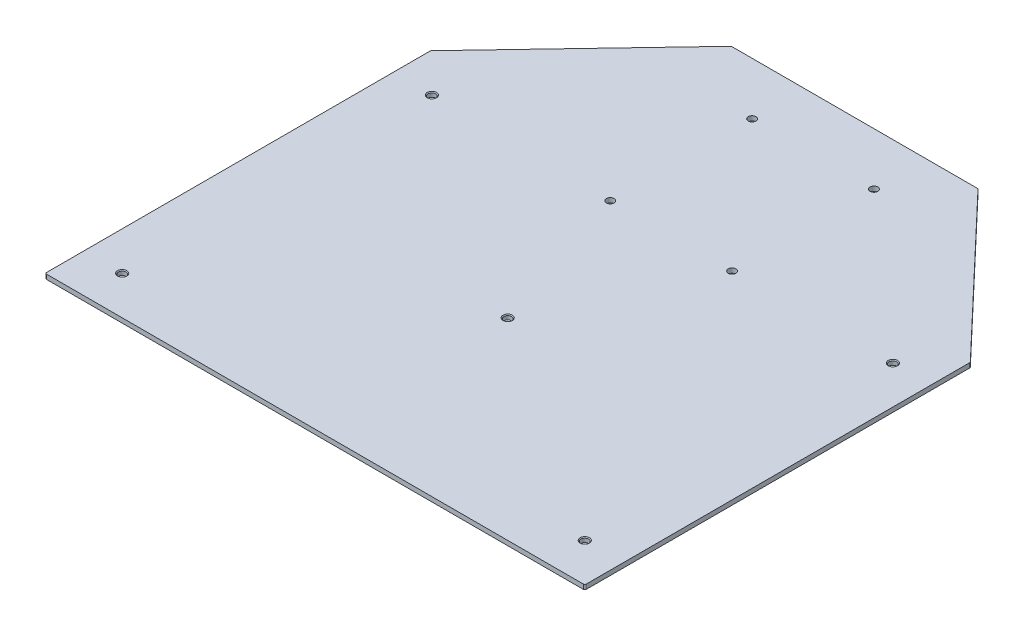
SolidWorks part; units mm, degrees
ref_plane "Front Plane" through (0, 0, 0) normal (0, 0, 1) x (1, 0, 0)
ref_plane "Top Plane" through (0, 0, 0) normal (0, 1, 0) x (1, 0, 0)
ref_plane "Right Plane" through (0, 0, 0) normal (1, 0, 0) x (0, 0, -1)
sketch "Plate Template" plane through (0, 0, 0) normal (0, 1, 0) x (1, 0, 0)
  line L0 (-79.5707, 225.0042) -> (79.5707, 225.0042)
  line L1 (-175, 125) -> (175, 125)
  line L2 (-175, 124.6007) -> (-175, -124)
  line L3 (-174, -125) -> (174, -125)
  line L4 (175, 124.6007) -> (175, -124)
  line L5 (-175, 125) -> (175, -125) construction
  line L6 (-175, -125) -> (175, 125) construction
  line L7 (-174.725, 125.2895) -> (-80.2957, 224.6929)
  line L8 (80.2957, 224.6929) -> (174.725, 125.2895)
  arc A0 (-174.725, 125.2895) -> (-175, 124.6007) centre (-174, 124.6007) ccw
  arc A1 (-175, -124) -> (-174, -125) centre (-174, -124) ccw
  arc A2 (175, -124) -> (174, -125) centre (174, -124) cw
  arc A3 (174.725, 125.2895) -> (175, 124.6007) centre (174, 124.6007) cw
  arc A4 (79.5707, 225.0042) -> (80.2957, 224.6929) centre (79.5707, 224.0042) cw
  arc A5 (-79.5707, 225.0042) -> (-80.2957, 224.6929) centre (-79.5707, 224.0042) ccw
  point P0 (0, 0)
  point P8 (0, 225.0042)
  point P9 (0, 125)
  point P24 (80, 225.0042)
  point P27 (-80, 225.0042)
  dimension "D5" = 1
  dimension "D1" = 350
  dimension "D2" = 250
  dimension "D3" = 160
  dimension "D4" = 136.47
extrude "Plate Extrude 1" add sketch "Plate Template" along normal blind 3 contours L7 A5 L0 A4 L8 A3 L4 A2 L3 A1 L2 A0
hole_wizard "M6 Tapped Hole2" positions "Sketch2" profile "Sketch3" tap size "M6" standard "ISO" end condition through all
sketch "Sketch2" plane through (0, 3, 0) normal (0, 1, 0) x (1, 0, 0)
  line L2 (-150, -100) -> (-150, -125)
  line L3 (-174, -125) -> (174, -125) construction
  line L4 (-150, -100) -> (150, -100)
  line L6 (-175, 124.6007) -> (-175, -124) construction
  line L7 (0, 0) -> (-175, 0.3004)
  line L9 (-149.6558, 100.5143) -> (150.3424, 99.4845)
  point P6 (-150, -100)
  point P15 (150, -100)
  point P20 (0, 0)
  point P27 (-149.6558, 100.5143)
  point P28 (150.3424, 99.4845)
  dimension "D1" = 25
  dimension "D2" = 300
  dimension "D3" = 25
sketch "Sketch3" plane through (-150, 3, 100) normal (1, 0, 0) x (0, 0, 1)
  line L0 (0, 0) -> (0, 3)
  line L1 (0, 3) -> (2.5, 3)
  line L2 (2.5, 3) -> (2.5, 0.525)
  line L3 (2.5, 0.525) -> (3.025, 0)
  line L5 (3.025, 0) -> (0, 0)
  line L6 (-2.5, 0.525) -> (-3.025, 0) construction
  line L11 (0, -6.35) -> (0, 107.95) construction
  dimension "Thru Tap Drill Dia." = 5
  dimension "Thru Tap Drill Depth" = 3
  dimension "Near C'Sink Dia." = 6.05
  dimension "Near C'Sink Angle" = 90
cosmetic thread "Hole Thread1" parameters "D2"=6
cosmetic thread "Hole Thread2" parameters "D2"=6
cosmetic thread "Hole Thread3" parameters "D2"=6
cosmetic thread "Hole Thread4" parameters "D2"=6
cosmetic thread "Hole Thread5" parameters "D2"=6
hole_wizard "Tap Drill for M6 Tap1" positions "Sketch4" profile "Sketch5" hole size "M6" standard "ISO"
sketch "Sketch4" plane through (0, 0, 0) normal (0, -1, 0) x (-1, 0, 0)
  line L0 (79.5707, 225.0042) -> (-79.5707, 225.0042) construction
  line L1 (175, 124.6007) -> (175, -124) construction
  point P0 (-46.5, 191.0042)
  point P3 (32.5, 191.0042)
  point P6 (32.5, 99.0042)
  point P9 (-46.5, 99.0042)
  dimension "D1" = 79
  dimension "D2" = 92
  dimension "D3" = 34
  dimension "D4" = 142.5
sketch "Sketch5" plane through (46.5, 0, -191.0042) normal (1, 0, 0) x (0, 0, -1)
  line L0 (0, 0) -> (0, 11.5022)
  line L1 (0, 11.5022) -> (2.5, 10)
  line L2 (2.5, 10) -> (2.5, 0.025)
  line L3 (2.5, 0.025) -> (2.525, 0)
  line L5 (2.525, 0) -> (0, 0)
  line L6 (-2.5, 0.025) -> (-2.525, 0) construction
  line L10 (0, 11.5022) -> (-2.5, 10) construction
  line L11 (0, -6.35) -> (0, 107.95) construction
  dimension "Hole Dia." = 5
  dimension "Hole Depth" = 10
  dimension "Near C'Sink Dia." = 5.05
  dimension "Near C'Sink Angle" = 90
  dimension "Drill Angle" = 118
